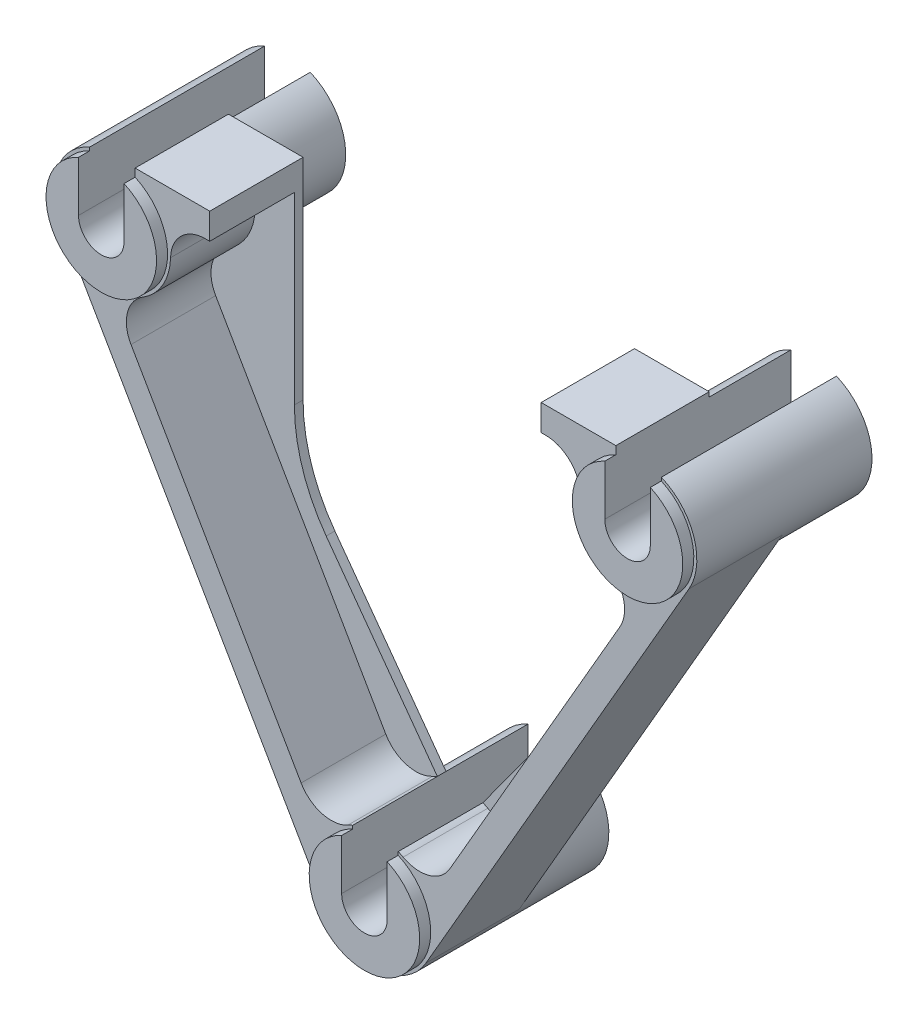
SolidWorks part; units mm, degrees
material "6061-T6 (SS)"
ref_plane "Front Plane" through (0, 0, 0) normal (0, 0, 1) x (1, 0, 0)
ref_plane "Top Plane" through (0, 0, 0) normal (0, 1, 0) x (1, 0, 0)
ref_plane "Right Plane" through (0, 0, 0) normal (1, 0, 0) x (0, 0, -1)
sketch "Sketch1" plane through (0, 0, 0) normal (0, 0, 1) x (1, 0, 0)
  line L0 (-30.2459, 17.4625) -> (30.2459, 17.4625) construction
  line L1 (30.2459, 17.4625) -> (0, -34.925) construction
  line L2 (0, -34.925) -> (-30.2459, 17.4625) construction
  line L3 (0, 0) -> (0, 17.4625) construction
  line L4 (0, 0) -> (-15.123, -8.7313) construction
  line L5 (0, 0) -> (15.123, -8.7313) construction
  line L6 (-40.8435, 22.4263) -> (-1, -46.5847)
  line L7 (-1, -46.5847) -> (1, -46.5847)
  line L8 (1, -46.5847) -> (40.8435, 22.4263)
  line L9 (40.8435, 22.4263) -> (39.8435, 24.1584)
  line L10 (39.8435, 24.1584) -> (-39.8435, 24.1584)
  line L11 (-39.8435, 24.1584) -> (-40.8435, 22.4263)
  line L12 (288.3643, 24.1584) -> (-29.7659, 24.1584) construction
  line L14 (0, 17.4625) -> (0, 24.1584) construction
  line L15 (15.123, -8.7313) -> (20.9218, -12.0792) construction
  circle A0 centre (-30.2459, 17.4625) radius 1.5
  circle A1 centre (30.2459, 17.4625) radius 1.5
  circle A2 centre (0, -34.925) radius 1.5
  circle A3 centre (0, 0) radius 34.925 construction
  dimension "D1" = 360
  dimension "D2" = 3
  dimension "D3" = 69.85
  dimension "D5" = 2
  dimension "D4" = 24.1584
extrude "Boss-Extrude1" add sketch "Sketch1" along normal blind 12
ref_axis "Axis1" through (0, 0, -7.125) along (0, 0, 1)
sketch "Sketch2" plane through (0, 0, 0) normal (0, 0, -1) x (-1, 0, 0)
  line L0 (40.8435, 22.4263) -> (1, -46.5847) construction
  circle A0 centre (30.2459, 17.4625) radius 6.6959
  circle A1 centre (-30.2459, 17.4625) radius 6.6959
  circle A2 centre (0, -34.925) radius 6.6959
extrude "Boss-Extrude2" add sketch "Sketch2" along normal blind 9.4028
sketch "Sketch3" plane through (0, 0, 0) normal (0, 0, -1) x (-1, 0, 0)
  line L0 (-5.7988, -38.2729) -> (-1, -46.5847) construction
  line L1 (-1, -46.5847) -> (1, -46.5847) construction
  line L2 (1, -46.5847) -> (5.7988, -38.2729) construction
  line L3 (-30.2459, 24.1584) -> (-39.8435, 24.1584) construction
  line L4 (-39.8435, 24.1584) -> (-40.8435, 22.4263) construction
  line L5 (-40.8435, 22.4263) -> (-36.0447, 14.1146) construction
  line L6 (36.0447, 14.1146) -> (40.8435, 22.4263) construction
  line L7 (40.8435, 22.4263) -> (39.8435, 24.1584) construction
  line L8 (39.8435, 24.1584) -> (30.2459, 24.1584) construction
  line L9 (-5.7988, -38.2729) -> (-1, -46.5847)
  line L10 (-1, -46.5847) -> (1, -46.5847)
  line L11 (1, -46.5847) -> (5.7988, -38.2729)
  line L12 (-30.2459, 24.1584) -> (-39.8435, 24.1584)
  line L13 (-39.8435, 24.1584) -> (-40.8435, 22.4263)
  line L14 (-40.8435, 22.4263) -> (-36.0447, 14.1146)
  line L15 (36.0447, 14.1146) -> (40.8435, 22.4263)
  line L16 (40.8435, 22.4263) -> (39.8435, 24.1584)
  line L17 (39.8435, 24.1584) -> (30.2459, 24.1584)
  arc A0 (-5.7988, -38.2729) -> (5.7988, -38.2729) centre (0, -34.925) ccw construction
  arc A1 (-30.2459, 24.1584) -> (-36.0447, 14.1146) centre (-30.2459, 17.4625) ccw construction
  arc A2 (36.0447, 14.1146) -> (30.2459, 24.1584) centre (30.2459, 17.4625) ccw construction
  arc A3 (-5.7988, -38.2729) -> (5.7988, -38.2729) centre (0, -34.925) ccw
  arc A4 (-30.2459, 24.1584) -> (-36.0447, 14.1146) centre (-30.2459, 17.4625) ccw
  arc A5 (36.0447, 14.1146) -> (30.2459, 24.1584) centre (30.2459, 17.4625) ccw
extrude "Cut-Extrude2" cut sketch "Sketch3" against normal through all
hole_wizard "Hole1" positions "Sketch4" profile "Sketch5" legacy end condition through all
sketch "Sketch4" plane through (0, 0, 12) normal (0, 0, 1) x (1, 0, 0)
  point P0 (-30.2459, 17.4625)
  point P3 (30.2459, 17.4625)
  point P6 (0, -34.925)
sketch "Sketch5" plane through (-30.2459, 17.4625, 12) normal (1, 0, 0) x (0, -1, 0)
  line L0 (0, 0) -> (0, 21.4028)
  line L1 (0, 21.4028) -> (2.6162, 21.4028)
  line L2 (2.6162, 21.4028) -> (2.6162, 0)
  line L3 (2.6162, 0) -> (0, 0)
  line L4 (0, 110) -> (0, -10) construction
  dimension "Diameter" = 5.2324
  dimension "Depth" = 21.4028
sketch "Sketch7" plane through (0, 0, 12) normal (0, 0, 1) x (1, 0, 0)
  line L0 (-19.5544, 21.1584) -> (19.5544, 21.1584)
  line L2 (28.1009, 6.3554) -> (8.5465, -27.5138)
  line L4 (-8.5465, -27.5138) -> (-28.1009, 6.3554)
  line L6 (30.2459, 24.1584) -> (-30.2459, 24.1584) construction
  line L7 (5.7988, -38.2729) -> (36.0447, 14.1146) construction
  line L8 (-36.0447, 14.1146) -> (-5.7988, -38.2729) construction
  arc A0 (30.2459, 24.1584) -> (36.0447, 14.1146) centre (30.2459, 17.4625) ccw construction
  arc A1 (-36.0447, 14.1146) -> (-30.2459, 24.1584) centre (-30.2459, 17.4625) ccw construction
  arc A2 (5.7988, -38.2729) -> (-5.7988, -38.2729) centre (0, -34.925) ccw construction
  arc A3 (23.5528, 17.2721) -> (26.7345, 11.7613) centre (30.2459, 17.4625) ccw
  arc A4 (-26.7345, 11.7613) -> (-23.5528, 17.2721) centre (-30.2459, 17.4625) ccw
  arc A5 (3.1817, -29.0334) -> (-3.1817, -29.0334) centre (0, -34.925) ccw
  arc A6 (-19.5544, 21.1584) -> (-23.5528, 17.2721) centre (-19.5544, 17.1584) ccw
  arc A7 (-26.7345, 11.7613) -> (-28.1009, 6.3554) centre (-24.6368, 8.3554) ccw
  arc A8 (23.5528, 17.2721) -> (19.5544, 21.1584) centre (19.5544, 17.1584) ccw
  arc A9 (26.7345, 11.7613) -> (28.1009, 6.3554) centre (24.6368, 8.3554) cw
  arc A10 (8.5465, -27.5138) -> (3.1817, -29.0334) centre (5.0824, -25.5138) cw
  arc A11 (-3.1817, -29.0334) -> (-8.5465, -27.5138) centre (-5.0824, -25.5138) cw
  dimension "D4" = 4
  dimension "D5" = 4
  dimension "D6" = 4
  dimension "D1" = 3
  dimension "D2" = 3
  dimension "D3" = 3
extrude "Cut-Extrude3" cut sketch "Sketch7" against normal offset from surface (11 mm away) 1 up to face at (0, 0, 0)
sketch "Sketch8" plane through (0, 0, 1) normal (0, 0, 1) x (1, 0, 0)
  circle A0 centre (0, 0) radius 19.05
  dimension "D1" = 38.1
extrude "Cut-Extrude4" cut sketch "Sketch8" against normal blind 10
sketch "Sketch9" plane through (0, 0, 12) normal (0, 0, 1) x (1, 0, 0)
  line L3 (5.7988, -38.2729) -> (36.0447, 14.1146)
  line L4 (30.2459, 24.1584) -> (-30.2459, 24.1584)
  line L5 (-36.0447, 14.1146) -> (-5.7988, -38.2729)
  line L6 (5.7988, -38.2729) -> (36.0447, 14.1146)
  line L7 (30.2459, 24.1584) -> (-30.2459, 24.1584)
  line L8 (-36.0447, 14.1146) -> (-5.7988, -38.2729)
  circle A0 centre (-30.2459, 17.4625) radius 6.35
  circle A1 centre (30.2459, 17.4625) radius 6.35
  circle A2 centre (0, -34.925) radius 6.35
  arc A6 (-5.7988, -38.2729) -> (5.7988, -38.2729) centre (0, -34.925) ccw
  arc A7 (36.0447, 14.1146) -> (30.2459, 24.1584) centre (30.2459, 17.4625) ccw
  arc A8 (-30.2459, 24.1584) -> (-36.0447, 14.1146) centre (-30.2459, 17.4625) ccw
  arc A9 (-5.7988, -38.2729) -> (5.7988, -38.2729) centre (0, -34.925) ccw
  arc A10 (36.0447, 14.1146) -> (30.2459, 24.1584) centre (30.2459, 17.4625) ccw
  arc A11 (-30.2459, 24.1584) -> (-36.0447, 14.1146) centre (-30.2459, 17.4625) ccw
  dimension "D1" = 12.7
  dimension "D2" = 0
extrude "Cut-Extrude6" cut sketch "Sketch9" against normal blind 1.27
sketch "Sketch10" plane through (0, 0, 12) normal (0, 0, 1) x (1, 0, 0)
  line L0 (-32.8621, 17.4625) -> (-32.8621, 23.6261)
  line L1 (-27.6297, 17.4625) -> (-27.6297, 24.1584)
  line L2 (30.2459, 24.1584) -> (-30.2459, 24.1584) construction
  line L3 (30.2459, 24.1584) -> (27.6297, 24.1584)
  line L4 (27.6297, 17.4625) -> (27.6297, 24.1584)
  line L5 (32.8621, 17.4625) -> (32.8621, 23.6261)
  line L6 (-27.6297, 24.1584) -> (-30.2459, 24.1584)
  line L7 (27.6297, 24.1584) -> (-27.6297, 24.1584) construction
  line L8 (27.6297, 24.1584) -> (27.6297, 25.7128) construction
  line L9 (32.8621, 23.6261) -> (32.8621, 26.2851) construction
  line L10 (-19.05, 0) -> (-19.05, 24.1584)
  line L11 (-19.05, 24.1584) -> (19.05, 24.1584)
  line L12 (19.05, 24.1584) -> (19.05, 0)
  line L13 (-2.6162, -34.925) -> (-2.6162, -28.7614)
  line L14 (2.6162, -34.925) -> (2.6162, -28.7614)
  line L17 (-15.3974, -11.2171) -> (-2.6162, -28.7614)
  line L19 (15.3974, -11.2171) -> (2.6162, -28.7614)
  circle A0 centre (0, -34.925) radius 2.6162 construction
  circle A1 centre (30.2459, 17.4625) radius 2.6162 construction
  circle A2 centre (-30.2459, 17.4625) radius 2.6162 construction
  arc A3 (-2.6162, -34.925) -> (2.6162, -34.925) centre (0, -34.925) ccw
  arc A4 (27.6297, 17.4625) -> (32.8621, 17.4625) centre (30.2459, 17.4625) ccw
  arc A5 (-32.8621, 17.4625) -> (-27.6297, 17.4625) centre (-30.2459, 17.4625) ccw
  arc A6 (-30.2459, 24.1584) -> (-36.0447, 14.1146) centre (-30.2459, 17.4625) ccw construction
  arc A7 (-30.2459, 24.1584) -> (-32.8621, 23.6261) centre (-30.2459, 17.4625) ccw
  arc A8 (36.0447, 14.1146) -> (30.2459, 24.1584) centre (30.2459, 17.4625) ccw construction
  arc A9 (32.8621, 23.6261) -> (30.2459, 24.1584) centre (30.2459, 17.4625) ccw
  arc A10 (36.0447, 14.1146) -> (32.8621, 23.6261) centre (30.2459, 17.4625) ccw construction
  arc A11 (32.8621, 17.4625) -> (27.6297, 17.4625) centre (30.2459, 17.4625) ccw construction
  arc A12 (-27.6297, 17.4625) -> (-32.8621, 17.4625) centre (-30.2459, 17.4625) ccw construction
  circle A13 centre (0, 0) radius 19.05 construction
  arc A14 (-19.05, 0) -> (-15.3974, -11.2171) centre (0, 0) ccw
  arc A15 (19.05, 0) -> (-19.05, 0) centre (0, 0) ccw construction
  arc A16 (3.1817, -29.0334) -> (-3.1817, -29.0334) centre (0, -34.925) ccw construction
  arc A17 (2.6162, -28.7614) -> (-2.6162, -28.7614) centre (0, -34.925) ccw construction
  arc A20 (2.6162, -34.925) -> (-2.6162, -34.925) centre (0, -34.925) ccw construction
  arc A21 (15.3974, -11.2171) -> (19.05, 0) centre (0, 0) ccw
  arc A22 (-15.3974, -11.2171) -> (15.3974, -11.2171) centre (0, 0) ccw construction
extrude "Cut-Extrude7" cut sketch "Sketch10" against normal through all
